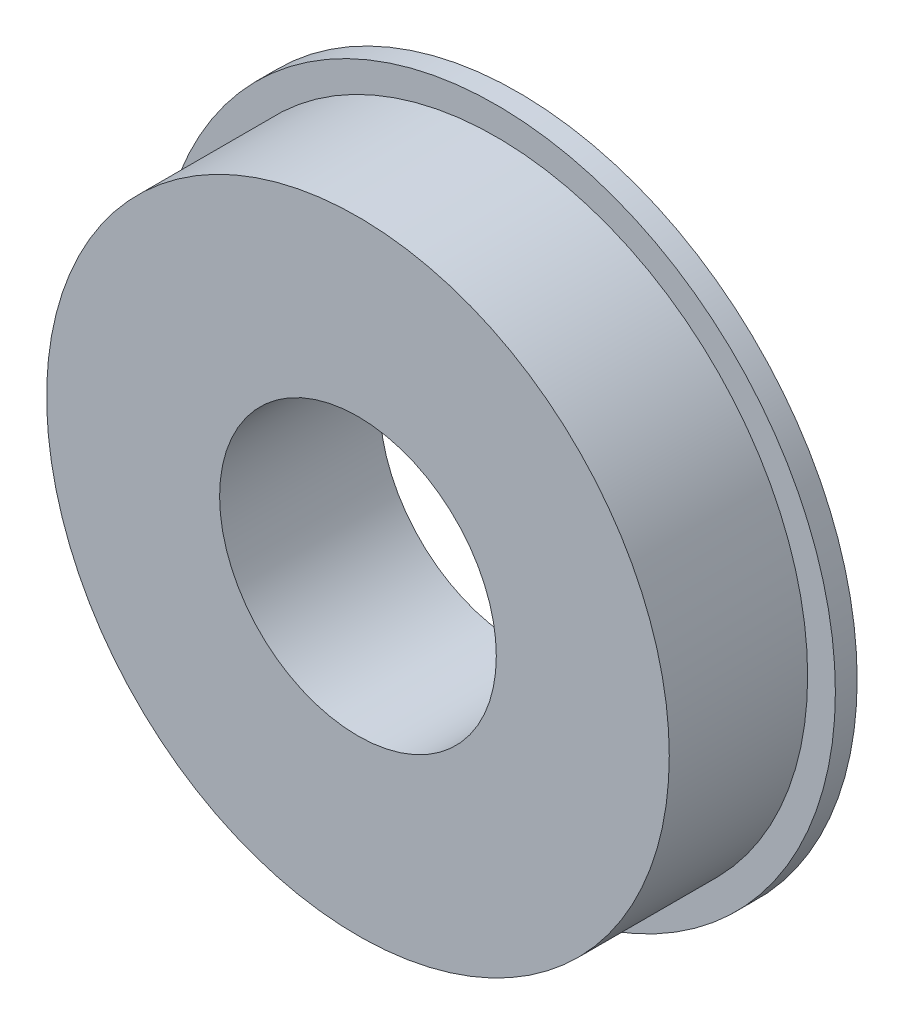
SolidWorks part; units mm, degrees
material "Alloy Steel"
ref_plane "Front Plane" through (0, 0, 0) normal (0, 0, 1) x (1, 0, 0)
ref_plane "Top Plane" through (0, 0, 0) normal (0, 1, 0) x (1, 0, 0)
ref_plane "Right Plane" through (0, 0, 0) normal (1, 0, 0) x (0, 0, -1)
sketch "Sketch1" plane through (0, 0, 0) normal (0, 0, 1) x (1, 0, 0)
  circle A0 centre (0, 0) radius 6.35
  circle A1 centre (0, 0) radius 14.2875
  circle A2 centre (0, 0) radius 15.56
  dimension "D1" = 12.7
  dimension "D2" = 28.575
  dimension "D3" = 31.1201
extrude "Boss-Extrude1" add sketch "Sketch1" along normal blind 7.35 contours A1 A0 region at (-13.8834, 0, 0)
extrude "Boss-Extrude2" add sketch "Sketch1<3>" along normal blind 1 contours A2 A1 region at (-15.1199, 0, 0)
sketch "Sketch1<3>" plane through (0, 0, 0) normal (0, 0, 1) x (1, 0, 0) same geometry as "Sketch1"
